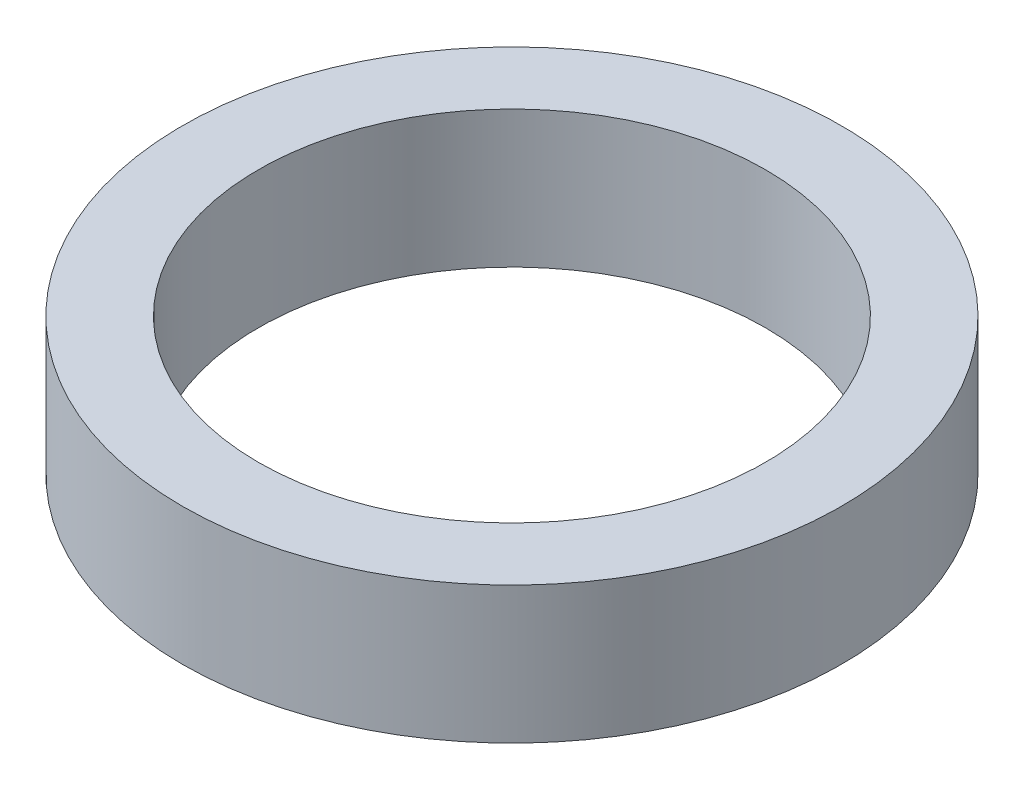
SolidWorks part; units mm, degrees
ref_plane "Front Plane" through (0, 0, 0) normal (0, 0, 1) x (1, 0, 0)
ref_plane "Top Plane" through (0, 0, 0) normal (0, 1, 0) x (1, 0, 0)
ref_plane "Right Plane" through (0, 0, 0) normal (1, 0, 0) x (0, 0, -1)
sketch "Sketch1" plane through (0, 0, 0) normal (0, 1, 0) x (1, 0, 0)
  circle A0 centre (0, 0) radius 65
  dimension "FLANGE_OD" = 130
extrude "Boss-Extrude1" add sketch "Sketch1" along normal blind 27
sketch "Sketch2" plane through (0, 0, 0) normal (0, 1, 0) x (1, 0, 0)
  circle A0 centre (0, 0) radius 50
  dimension "BORE_D" = 100
extrude "Cut-Extrude1" cut sketch "Sketch2" along normal through all
sketch "Sketch3" plane through (0, 27, 0) normal (0, 1, 0) x (1, 0, 0)
  circle A0 centre (0, 0) radius 28.2685 construction
  circle A1 centre (-28.2685, 0) radius 1.6679
  dimension "BOLT_D" = 3.3358
  dimension "BOLT_PCD" = 56.5369
extrude "Cut-Extrude2" cut sketch "Sketch3" against normal blind 18.714 rebuild error yes
pattern_circular "CirPattern1" count 5 over 360 rebuild error yes
